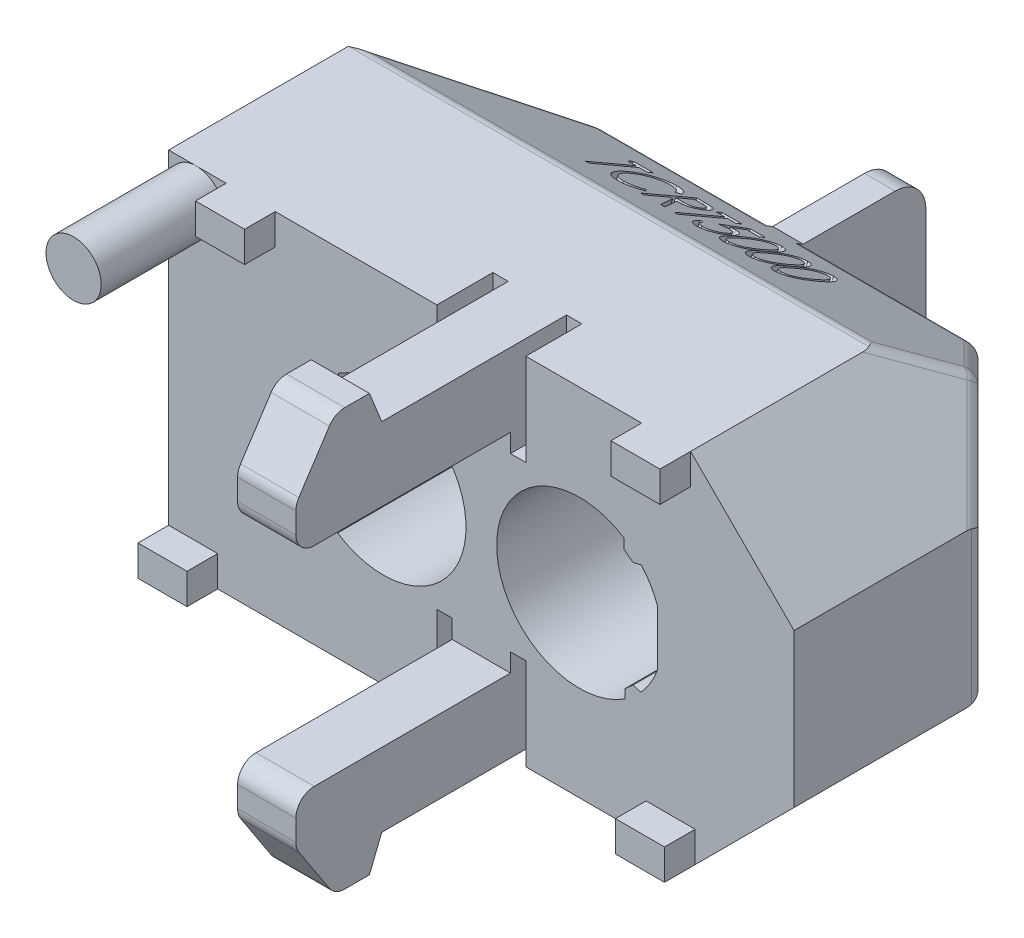
SolidWorks part; units mm, degrees
ref_plane "Plano frontal" through (0, 0, 0) normal (0, 0, 1) x (1, 0, 0)
ref_plane "Plano superior" through (0, 0, 0) normal (0, 1, 0) x (1, 0, 0)
ref_plane "Plano direito" through (0, 0, 0) normal (1, 0, 0) x (0, 0, -1)
sketch "Esboço1" plane through (0, 0, 0) normal (0, 0, 1) x (1, 0, 0)
  line L0 (1.6297, 5.8) -> (0, 5.8)
  line L1 (10.2, 4.113) -> (8.513, 5.8)
  line L2 (1.6703, 0) -> (8.587, 0)
  line L3 (0, 1.6703) -> (0, 4.1703)
  line L4 (1.6297, 5.8) -> (8.513, 5.8)
  line L5 (10.2, 1.613) -> (10.2, 4.113)
  line L6 (10.2, 1.613) -> (8.587, 0)
  line L9 (0, 5.8) -> (0, 4.1703)
  line L10 (0, 0) -> (1.6703, 0)
  line L11 (0, 1.6703) -> (0, 0)
  dimension "D3" = 45
  dimension "D4" = 45
  dimension "D5" = 2.5
  dimension "D8" = 2.5
extrude "Ressalto-extrusão1" add sketch "Esboço1" along normal blind 3
ref_plane "Plano meio do tcrt" through (5.1, 0, 0) normal (-1, 0, 0) x (0, 0, 1)
sketch "Esboço2" plane through (5.1, 0, 0) normal (-1, 0, 0) x (0, 0, 1)
  line L1 (3, 5.8) -> (3, 0) construction
  line L2 (5.3, 6.3) -> (5.1, 5.8)
  line L3 (5.8646, 6.3) -> (5.3, 6.3)
  line L4 (6.5, 5.3296) -> (5.8646, 6.3)
  line L6 (6.5, 4.6) -> (6.5, 5.3296)
  line L8 (3, 0) -> (0, 0) construction
  line L9 (3, 1.2) -> (6.5, 1.2)
  line L10 (3, 1.2) -> (3, 0)
  line L11 (3, 0) -> (5.1, 0)
  line L12 (6.5, 1.2) -> (6.5, 0.4704)
  line L13 (6.5, 0.4704) -> (5.8646, -0.5)
  line L14 (5.8646, -0.5) -> (5.3, -0.5)
  line L15 (5.3, -0.5) -> (5.1, 0)
  line L16 (3, 2.9) -> (6.5, 2.9) construction
  line L17 (3, 5.8) -> (5.1, 5.8)
  line L18 (3, 4.6) -> (3, 5.8)
  line L19 (3, 4.6) -> (6.5, 4.6)
  dimension "D1" = 2.1
  dimension "D4" = 2.3
extrude "Ressalto-extrusão2" add sketch "Esboço2" along normal blind 0.475 and the other way blind 0.475
fillet "Filete1" radius 0.3 6 edges at (5.1, 6.3, 5.8646) (5.1, -0.5, 5.8646) (5.1, 1.2, 6.5) (5.1, 4.6, 6.5) (5.1, 5.3296, 6.5) (5.1, 0.4704, 6.5)
sketch "Esboço3" plane through (0, 0, 3) normal (0, 0, 1) x (1, 0, 0)
  line L2 (0, 0.5) -> (0.8, 0.5)
  line L3 (0, 0.5) -> (0, 0)
  line L4 (0, 0) -> (0.8, 0)
  line L7 (0.8, 0.5) -> (0.8, 0)
  line L12 (8.513, 5.8) -> (7.713, 5.8)
  line L13 (8.513, 5.8) -> (8.513, 5.3)
  line L14 (8.513, 5.3) -> (7.713, 5.3)
  line L15 (7.713, 5.8) -> (7.713, 5.3)
  line L16 (8.587, 0) -> (7.787, 0)
  line L17 (8.587, 0) -> (8.587, 0.5)
  line L18 (8.587, 0.5) -> (7.787, 0.5)
  line L19 (7.787, 0) -> (7.787, 0.5)
  point P4 (0, 0)
  point P5 (0, 0)
  dimension "D1" = 0.8
  dimension "D2" = 0.5
  dimension "D3" = 0.8
  dimension "D4" = 0.5
  dimension "D5" = 0.8
  dimension "D6" = 0.5
extrude "Ressalto-extrusão3" add sketch "Esboço3" along normal blind 0.5
sketch "Esboço4" plane through (0, 0, 3) normal (0, 0, 1) x (1, 0, 0)
  line L2 (0, 5.8) -> (0, 0.5) construction
  line L4 (4.625, 5.8) -> (0, 5.8) construction
  circle A0 centre (0.45, 5.35) radius 0.45
  point P6 (0, 0)
  dimension "D1" = 0.9
sketch "Esboço5" plane through (0, 0, 3) normal (0, 0, 1) x (1, 0, 0)
  line L0 (4.625, 5.8) -> (0, 5.8) construction
  line L1 (1.7387, 5.8) -> (0.9387, 5.8)
  line L2 (1.7387, 5.8) -> (1.7387, 5.3)
  line L3 (1.7387, 5.3) -> (0.9387, 5.3)
  line L4 (0.9387, 5.8) -> (0.9387, 5.3)
  point P6 (0, 0)
  dimension "D1" = 0.5
  dimension "D2" = 0.8
extrude "Ressalto-extrusão5" add sketch "Esboço5" along normal blind 0.5
sketch "Esboço6" plane through (0, 5.8, 0) normal (0, 1, 0) x (1, 0, 0)
  line L1 (4.625, -3) -> (4.375, -3)
  line L2 (4.625, -3) -> (4.625, -2.0862)
  line L3 (4.625, -2.0862) -> (4.375, -2.0862)
  line L4 (4.375, -3) -> (4.375, -2.0862)
  line L5 (5.575, -3) -> (5.825, -3)
  line L6 (5.575, -3) -> (5.575, -2.0862)
  line L7 (5.575, -2.0862) -> (5.825, -2.0862)
  line L8 (5.825, -3) -> (5.825, -2.0862)
  dimension "D1" = 0.25
  dimension "D2" = 0.25
extrude "Corte-extrusão1" cut sketch "Esboço6" against normal blind 1.5
sketch "Esboço7" plane through (0, 0, 0) normal (0, -1, 0) x (-1, 0, 0)
  line L1 (-5.575, -3) -> (-5.825, -3)
  line L2 (-5.575, -3) -> (-5.575, -2)
  line L3 (-5.575, -2) -> (-5.825, -2)
  line L4 (-5.825, -3) -> (-5.825, -2)
  line L5 (-4.625, -3) -> (-4.375, -3)
  line L6 (-4.625, -3) -> (-4.625, -2)
  line L7 (-4.625, -2) -> (-4.375, -2)
  line L8 (-4.375, -3) -> (-4.375, -2)
  dimension "D1" = 0.25
  dimension "D2" = 0.25
  dimension "D3" = 1
extrude "Corte-extrusão2" cut sketch "Esboço7" against normal blind 1.5
sketch "Esboço8" plane through (0, 0, 0) normal (0, -1, 0) x (-1, 0, 0)
  line L0 (-10.2, 0) -> (-8.2, 2)
  line L1 (-8.2, 2) -> (-2, 2)
  line L2 (-2, 2) -> (0, 0)
  line L3 (-8.587, 0) -> (-10.2, 0) construction
  line L4 (0, 0) -> (-8.587, 0) construction
  line L5 (-10.2, 0) -> (0, 0)
  dimension "D1" = 45
  dimension "D2" = 45
  dimension "D3" = 2
extrude "Ressalto-extrusão6" add sketch "Esboço8" against normal blind 5.8
sketch "Esboço9" plane through (0, 0, 0) normal (0, 0, 1) x (1, 0, 0)
  line L0 (8.587, 0) -> (10.2, 0)
  line L1 (10.2, 0) -> (10.2, 1.613)
  line L2 (10.2, 1.613) -> (8.587, 0)
  line L3 (8.513, 5.8) -> (10.2, 5.8)
  line L4 (10.2, 5.8) -> (10.2, 4.113) construction
  line L5 (10.2, 5.8) -> (10.2, 4.113)
  line L6 (10.2, 4.113) -> (8.513, 5.8)
extrude "Corte-extrusão3" cut sketch "Esboço9" against normal through all
sketch "Esboço10" plane through (0, 0, 0) normal (-1, 0, 0) x (0, 0, 1)
  line L0 (-2, 0) -> (-2, 1.1547)
  line L2 (-2, 5.8) -> (-2, 0) construction
  line L3 (-2, 1.1547) -> (0, 0)
  line L4 (0, 0) -> (-2, 0)
  line L5 (-2, 5.8) -> (-2, 4.6453)
  line L6 (-2, 4.6453) -> (0, 5.8)
  line L7 (0, 5.8) -> (-2, 5.8)
  dimension "D1" = 30
  dimension "D2" = 30
extrude "Corte-extrusão4" cut sketch "Esboço10" against normal through all
sketch "Esboço12" plane through (5.1, 0, 0) normal (-1, 0, 0) x (0, 0, 1)
  line L1 (-2, 4.6453) -> (-4, 4.6453)
  line L2 (-2, 4.6453) -> (-2, 1.1547)
  line L3 (-2, 1.1547) -> (-4, 1.1547)
  line L4 (-4, 4.6453) -> (-4, 1.1547)
  dimension "D1" = 2
extrude "Ressalto-extrusão7" add sketch "Esboço12" along normal blind 0.25 and the other way blind 0.25
fillet "Filete3" radius 0.5 2 edges at (5.1, 4.6453, -4) (5.1, 1.1547, -4)
fillet "Filete5" radius 0.25 17 edges at (4.2565, 5.8, 0) (8.6652, 4.9139, -1.5348) (2, 2.9, -2) (1, 5.2226, -1) (4.2935, 0, 0) (8.8822, 0.2952, -0.5113) (8.6887, 0.8725, -1.5113) (8.2, 2.9, -2) (1, 0.5774, -1) (8.8217, 5.4912, -0.5348)
sketch "Esboço11" plane through (0, 0, 3) normal (0, 0, 1) x (1, 0, 0)
  line L1 (5.35, 4.1453) -> (5.35, 1.6547) construction
  line L3 (5.1, 1.1542) -> (5.1, 4.6367) construction
  line L4 (5.1, 3.0298) -> (5.1, -3.0298) construction
  circle A0 centre (6.7, 2.8962) radius 1.35
  circle A1 centre (3.5, 2.8962) radius 1.35
  dimension "D1" = 2.7
extrude "Corte-extrusão7" cut sketch "Esboço11" against normal through all
sketch "Esboço14" plane through (0, 0, -2) normal (0, 0, -1) x (-1, 0, 0)
  line L0 (-7.4286, 4.0327) -> (-7.4286, 3.8708)
  line L1 (-7.4286, 3.8708) -> (-7.5736, 3.7623)
  line L2 (-7.5736, 3.7623) -> (-7.7079, 3.7943)
  line L3 (-7.9732, 3.3449) -> (-7.9732, 2.4475)
  line L4 (-7.7025, 1.9921) -> (-7.5736, 2.0295)
  line L5 (-7.5736, 2.0295) -> (-7.4436, 1.915)
  line L6 (-7.4436, 1.915) -> (-7.4436, 1.7695)
  line L7 (-5.1, 4.1453) -> (-5.1, 1.6547) construction
  line L8 (-4.85, 4.1453) -> (-5.35, 4.1453) construction
  line L9 (-5.35, 1.6547) -> (-4.85, 1.6547) construction
  line L10 (-2.7564, 1.915) -> (-2.7564, 1.7695)
  line L11 (-2.6264, 2.0295) -> (-2.7564, 1.915)
  line L12 (-2.4975, 1.9921) -> (-2.6264, 2.0295)
  line L13 (-2.2268, 3.3449) -> (-2.2268, 2.4475)
  line L14 (-2.6264, 3.7623) -> (-2.4921, 3.7943)
  line L15 (-2.7714, 3.8708) -> (-2.6264, 3.7623)
  line L16 (-2.7714, 4.0327) -> (-2.7714, 3.8708)
  circle A0 centre (-6.7, 2.8962) radius 1.35 construction
  arc A1 (-7.4286, 4.0327) -> (-7.7079, 3.7943) centre (-6.7, 2.8962) ccw
  arc A2 (-7.9732, 3.3449) -> (-7.9732, 2.4475) centre (-6.7, 2.8962) ccw
  arc A3 (-7.7025, 1.9921) -> (-7.4436, 1.7695) centre (-6.7, 2.8962) ccw
  arc A4 (-2.4975, 1.9921) -> (-2.7564, 1.7695) centre (-3.5, 2.8962) cw
  arc A5 (-2.2268, 3.3449) -> (-2.2268, 2.4475) centre (-3.5, 2.8962) cw
  arc A6 (-2.7714, 4.0327) -> (-2.4921, 3.7943) centre (-3.5, 2.8962) cw
extrude "Ressalto-extrusão8" add sketch "Esboço14" against normal blind 5
sketch "Esboço16" plane through (0, 4.35, -2.5115) normal (0, 0.866, -0.5) x (1, 0, 0)
  text T0 "TCRT5000" font "Century Gothic" height in points 4
extrude "Corte-extrusão8" cut sketch "Esboço16" against normal blind 0.5
surface "Surface-Extrude1" sketch "Esboço4" parameters "D1"=2
surface "Surface-Fill1"
